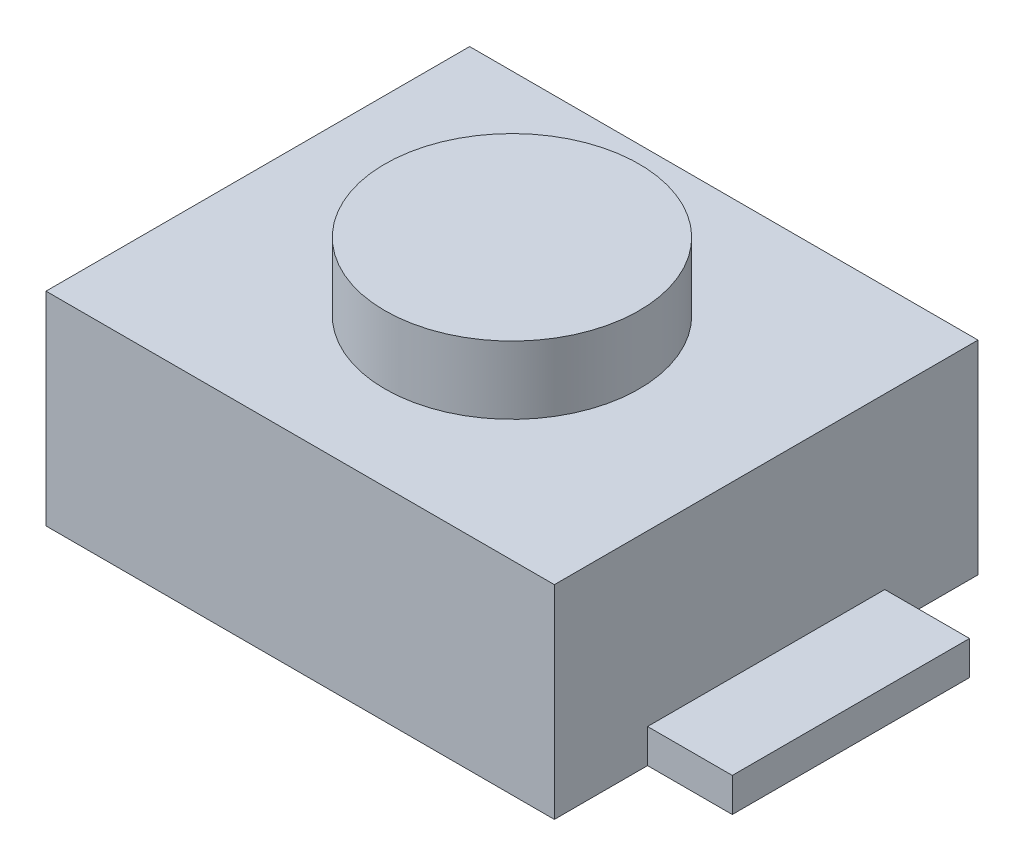
SolidWorks part; units mm, degrees
ref_plane "Front Plane" through (0, 0, 0) normal (0, 0, 1) x (1, 0, 0)
ref_plane "Top Plane" through (0, 0, 0) normal (0, 1, 0) x (1, 0, 0)
ref_plane "Right Plane" through (0, 0, 0) normal (1, 0, 0) x (0, 0, -1)
ref_plane "Plane1" through (0, 0, 0) normal (0, -1, 0) x (1, 0, 0)
sketch "Sketch1" plane through (0, 0, 0) normal (0, -1, 0) x (1, 0, 0)
  line L0 (1.5, -1.25) -> (1.5, 1.25)
  line L1 (1.5, 1.25) -> (-1.5, 1.25)
  line L2 (-1.5, 1.25) -> (-1.5, -1.25)
  line L3 (-1.5, -1.25) -> (1.5, -1.25)
extrude "Boss-Extrude1" add sketch "Sketch1" against normal blind 1.2
sketch "Sketch2" plane through (1.5, 0, 0) normal (1, 0, 0) x (0, 0, -1)
  line L0 (0.7, 0.2) -> (0.7, 0)
  line L1 (0.7, 0) -> (-0.7, 0)
  line L2 (-0.7, 0) -> (-0.7, 0.2)
  line L3 (-0.7, 0.2) -> (0.7, 0.2)
extrude "Boss-Extrude2" add sketch "Sketch2" along normal blind 0.5
sketch "Sketch3" plane through (-1.5, 0, 0) normal (-1, 0, 0) x (0, 0, 1)
  line L0 (0.7, 0) -> (-0.7, 0)
  line L1 (-0.7, 0) -> (-0.7, 0.2)
  line L2 (-0.7, 0.2) -> (0.7, 0.2)
  line L3 (0.7, 0.2) -> (0.7, 0)
extrude "Boss-Extrude3" add sketch "Sketch3" along normal blind 0.5
ref_plane "Plane2" through (0, 0, 0) normal (0, 0, -1) x (-1, 0, 0)
sketch "Sketch4" plane through (0, 0, 0) normal (0, 0, -1) x (-1, 0, 0)
  line L0 (-0.75, 1.2) -> (0, 1.2)
  line L1 (0, 1.2) -> (0, 1.6)
  line L2 (0, 1.6) -> (-0.75, 1.6)
  line L3 (-0.75, 1.6) -> (-0.75, 1.2)
  line L4 (0, 1.2) -> (0, 1.6) construction
revolve "Revolve1" add sketch "Sketch4" angle 360 about L4 reverse direction yes
